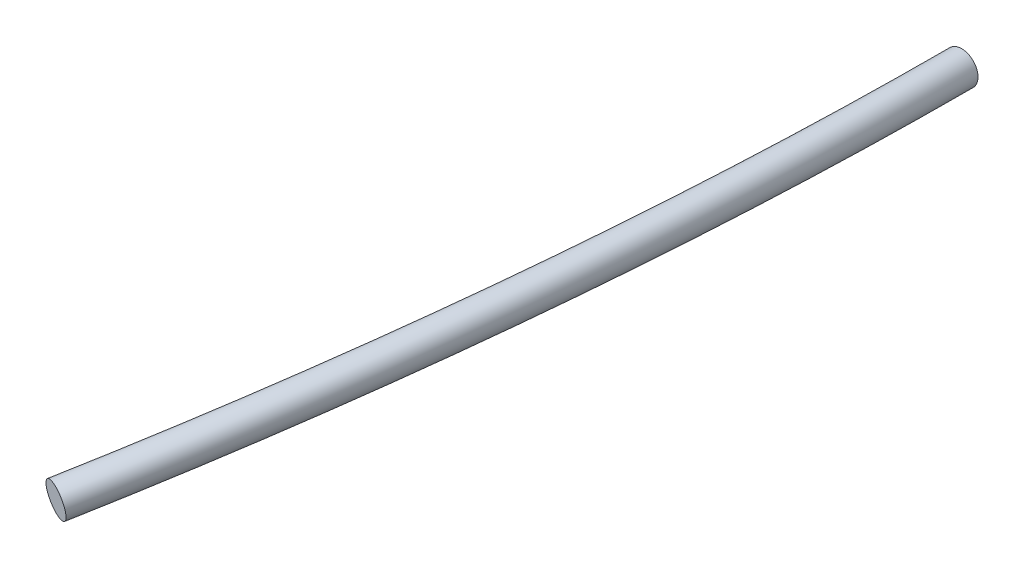
SolidWorks part; units mm, degrees
ref_plane "Front" through (0, 0, 0) normal (0, 0, 1) x (1, 0, 0)
ref_plane "Top" through (0, 0, 0) normal (0, 1, 0) x (1, 0, 0)
ref_plane "Right" through (0, 0, 0) normal (1, 0, 0) x (0, 0, -1)
sketch "Sketch1" plane through (0, 0, 0) normal (0, 0, 1) x (1, 0, 0)
  circle A0 centre (3795.5943, 6781.3906) radius 50.8
ref_plane "Plane1" through (-1887.3719, 4268.7295, 0) normal (0.4044, -0.9146, 0) x (0.9146, 0.4044, 0)
sketch "Sketch2" plane through (-1887.3719, 4268.7295, 0) normal (0.4044, -0.9146, 0) x (0.9146, 0.4044, 0)
  line L0 (6213.66, 0) -> (6213.66, 5294.7528) construction
  line L1 (6264.46, 0) -> (6162.86, 0) construction
  line L2 (5737.699, 2375.3207) -> (5611.9908, 2676.4044) construction
  line L3 (6213.66, 0) -> (5737.699, 2375.3207) construction
  line L4 (5975.6795, 1187.6603) -> (6093.4987, 1211.2687) construction
  arc A0 (6213.66, 0) -> (5737.699, 2375.3207) centre (48.5676, 0) ccw
  point P3 (6187.3054, 569.4403)
  point P8 (6056.1984, 1384.4625)
  point P9 (5817.3808, 2174.6628)
  dimension "D1" = 2438.4
  dimension "D3" = 825.5
  dimension "D2" = 215.9
  dimension "D4" = 825.5
  dimension "D5" = 120.1613
  dimension "D6" = 2743.2
sweep "Sweep1" add profiles "Sketch1" path "Sketch2"
ref_plane "rib1_plane" through (3771.4906, 6770.7334, 569.4403) normal (-0.0845, -0.0374, 0.9957) x (0.9964, -0.0032, 0.0844)
ref_point "rib1_point"
ref_plane "rib2_plane" through (3651.5812, 6717.7167, 1384.4625) normal (-0.2054, -0.0908, 0.9745) x (0.9787, -0.0191, 0.2045)
ref_point "rib2_point"
ref_plane "rib3_plane" through (3433.1604, 6621.1444, 2174.6628) normal (-0.3226, -0.1426, 0.9357) x (0.9465, -0.0486, 0.3189)
ref_point "rib3_point"
ref_point "Point1"
ref_plane "Plane2" through (-1451.4161, 1605.9269, -834.1587) normal (-0.6257, 0.6923, -0.3596) x (-0.7801, -0.5552, 0.2884)
ref_axis "Axis1" through (12185.6381, 14364.2045, 0) along (-0.7419, -0.6705, 0)
ref_point "Point2"
ref_plane "Plane3" through (-1004.0599, 1110.9473, -577.0539) normal (0.6257, -0.6923, 0.3596) x (0.7801, 0.5552, -0.2884)
ref_axis "Axis2" through (3315.2701, 6534.5425, 2348.9504) along (0.5973, 0.7216, 0.3499)
sketch "Sketch3" plane through (6.5939, 2.9154, -17.2678) normal (-0.3524, -0.1558, 0.9228) x (0.9359, -0.0587, 0.3475)
  line L0 (3551.1244, 6853.3091) -> (3615.9728, 6931.5219)
  line L3 (3537.7357, 6870.4652) -> (3629.3615, 6914.3658)
  line L4 (-7759.7981, 1457.489) -> (3726.3373, 6960.8297) construction
  line L5 (3535.4495, 6834.4039) -> (3631.6477, 6950.4271) construction
  circle A0 centre (3583.5486, 6892.4155) radius 50.8 construction
  point P10 (3583.5486, 6892.4155)
  dimension "D1" = 24.736
sketch "Sketch4" plane through (0, 0, 0) normal (0, 0, -1) x (-1, 0, 0)
  line L0 (-3757.9061, 6747.3284) -> (-3833.2826, 6815.4528)
  line L1 (-12185.6381, 14364.2045) -> (12473.4128, -7922.3294) construction
  line L2 (-3842.0556, 6801.9329) -> (-3749.133, 6760.8482)
  line L3 (-3936.9746, 6843.9003) -> (7711.7183, 1693.5587) construction
  line L4 (-3471.5526, 6676.7175) -> (-3407.1858, 6577.7927)
  circle A1 centre (-3795.5943, 6781.3906) radius 50.8 construction
  ellipse E1 centre (-3360.284, 6588.9229) end of major axis (-3380.8264, 6542.4616) minor radius 46.8781 construction
  point P4 (-3795.5943, 6781.3906)
  dimension "D1" = 18.255
